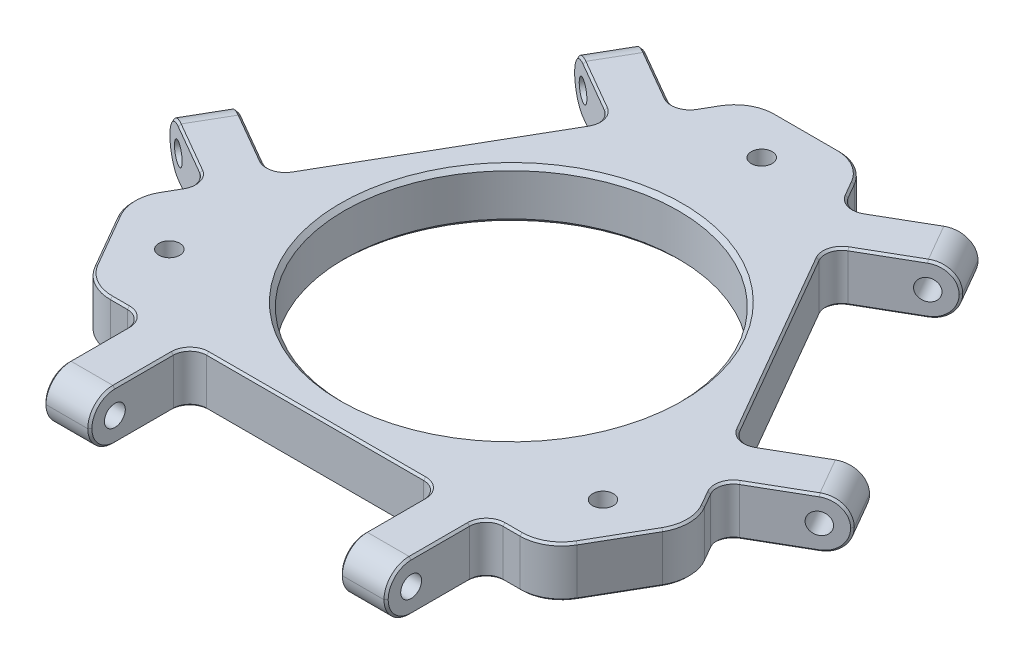
SolidWorks part; units mm, degrees
material "6061-T6 (SS)"
ref_plane "Front Plane" through (0, 0, 0) normal (0, 0, 1) x (1, 0, 0)
ref_plane "Top Plane" through (0, 0, 0) normal (0, 1, 0) x (1, 0, 0)
ref_plane "Right Plane" through (0, 0, 0) normal (1, 0, 0) x (0, 0, -1)
sketch "Sketch1" plane through (0, 0, 0) normal (0, 1, 0) x (1, 0, 0)
  line L1 (-20.5, 35.507) -> (-41, 0)
  line L2 (-41, 0) -> (-20.5, -35.507)
  line L3 (-20.5, -35.507) -> (20.5, -35.507)
  line L4 (20.5, -35.507) -> (41, 0)
  line L5 (41, 0) -> (20.5, 35.507)
  line L6 (20.5, 35.507) -> (-20.5, 35.507)
  circle A1 centre (0, 0) radius 35.507 construction
  dimension "D1" = 41
  dimension "D2" = 71.0141
extrude "Boss-Extrude1" add sketch "Sketch1" along normal blind 6
sketch "Sketch2" plane through (0, 6, 0) normal (0, 1, 0) x (1, 0, 0)
  line L0 (-20.5, -35.507) -> (-20.5, -23.507)
  line L1 (-20.5, -23.507) -> (-27.4282, -23.507)
  line L2 (20.5, -35.507) -> (20.5, -23.507)
  line L3 (20.5, -23.507) -> (27.4282, -23.507)
  line L4 (-20.5, -23.507) -> (-15, -23.507) construction
  line L5 (-15, -35.507) -> (15, -35.507)
  line L6 (20.5, 35.507) -> (-20.5, 35.507)
  line L7 (-20.5, 35.507) -> (-41, 0)
  line L8 (-41, 0) -> (-20.5, -35.507)
  line L9 (-20.5, -35.507) -> (20.5, -35.507)
  line L10 (20.5, -35.507) -> (41, 0)
  line L11 (41, 0) -> (20.5, 35.507)
  line L12 (20.5, 35.507) -> (-20.5, 35.507) construction
  line L13 (-20.5, 35.507) -> (-41, 0) construction
  line L14 (-41, 0) -> (-20.5, -35.507) construction
  line L15 (-20.5, -35.507) -> (20.5, -35.507) construction
  line L16 (20.5, -35.507) -> (41, 0) construction
  line L17 (41, 0) -> (20.5, 35.507) construction
  line L18 (-15, -35.507) -> (-15, -23.507)
  line L19 (-15, -23.507) -> (15, -23.507)
  line L20 (15, -35.507) -> (15, -23.507)
  line L21 (15, -23.507) -> (20.5, -23.507) construction
  line L22 (-27.4282, -23.507) -> (-20.5, -35.507)
  line L23 (27.4282, -23.507) -> (20.5, -35.507)
  line L24 (0, 0) -> (0, -35.507) construction
  line L25 (-20.5, 35.507) -> (-10.1077, 29.507)
  line L26 (-10.1077, 29.507) -> (-6.6436, 35.507)
  line L27 (-41, 0) -> (-30.6077, -6)
  line L28 (-30.6077, -6) -> (-34.0718, -12)
  line L29 (-23.25, 30.7439) -> (-38.25, 4.7631)
  line L30 (-23.25, 30.7439) -> (-12.8577, 24.7439)
  line L31 (-12.8577, 24.7439) -> (-27.8577, -1.2369)
  line L32 (-38.25, 4.7631) -> (-27.8577, -1.2369)
  line L33 (-6.6436, 35.507) -> (-20.5, 35.507)
  line L34 (-34.0718, -12) -> (-41, 0)
  line L35 (41, 0) -> (30.6077, -6)
  line L36 (30.6077, -6) -> (34.0718, -12)
  line L37 (20.5, 35.507) -> (10.1077, 29.507)
  line L38 (10.1077, 29.507) -> (6.6436, 35.507)
  line L39 (38.25, 4.7631) -> (23.25, 30.7439)
  line L40 (38.25, 4.7631) -> (27.8577, -1.2369)
  line L41 (27.8577, -1.2369) -> (12.8577, 24.7439)
  line L42 (23.25, 30.7439) -> (12.8577, 24.7439)
  line L43 (34.0718, -12) -> (41, 0)
  line L44 (6.6436, 35.507) -> (20.5, 35.507)
  point P14 (0, -23.507)
  point P41 (0, 0)
  dimension "D2" = 30
  dimension "D3" = 12
  dimension "D1" = 0
  dimension "D4" = 3
extrude "Cut-Extrude1" cut sketch "Sketch2" against normal through all
sketch "Sketch3" plane through (-20.5, 0, 0) normal (-1, 0, 0) x (0, 0, 1)
  line L0 (35.507, 3) -> (23.507, 3) construction
  line L1 (35.507, 6) -> (35.507, 0) construction
  line L2 (23.507, 0) -> (23.507, 6) construction
  line L3 (32.507, 6) -> (32.507, 0) construction
  line L4 (35.507, 6) -> (23.507, 6) construction
  line L5 (35.507, 0) -> (23.507, 0) construction
  point P12 (32.507, 3)
  dimension "D1" = 3
hole_wizard "M3x0.5 Tapped Hole1" positions "Sketch7" profile "Sketch6" tap size "M3x0.5" standard "ANSI Metric" end condition up to next
sketch "Sketch7" plane through (-20.5, 0, 0) normal (-1, 0, 0) x (0, 0, 1)
  point P0 (32.507, 3)
sketch "Sketch6" plane through (-20.5, 3, 32.507) normal (0, 1, 0) x (0, 0, 1)
  line L0 (0, 0) -> (0, 10.6975)
  line L1 (0, 10.6975) -> (1.25, 10.6975)
  line L2 (1.25, 10.6975) -> (1.25, 0)
  line L5 (1.25, 0) -> (0, 0)
  line L11 (0, -6.35) -> (0, 107.95) construction
  dimension "Thru Tap Drill Dia." = 2.5
  dimension "Thru Tap Drill Depth" = 10.6975
cosmetic thread "Hole Thread1" parameters "D2"=3
mirror "Mirror1" about plane through (0, 0, 0) normal (1, 0, 0) of "M3x0.5 Tapped Hole1"
ref_axis "Axis1" through (0, 0, 0) along (0, 1, 0)
pattern_circular "CirPattern1" count 3 over 360 about axis through (0, 0, 0) along (0, 1, 0) of "M3x0.5 Tapped Hole1", "Mirror1"
fillet "Fillet1" radius 3 12 edges at (-39.625, 0, -2.3816) (-21.875, 0, -33.1255) (17.75, 0, 35.507) (-17.75, 0, 35.507) (21.875, 0, -33.1255) (39.625, 0, -2.3816) (-39.625, 6, -2.3816) (17.75, 6, 35.507) (-17.75, 6, 35.507) (21.875, 6, -33.1255) (39.625, 6, -2.3816) (-21.875, 6, -33.1255)
sketch "Sketch9" plane through (0, 0, 0) normal (0, 1, 0) x (1, 0, 0)
  line L0 (0, 0) -> (-25.9808, -15) construction
  line L1 (0, 0) -> (0, 30) construction
  line L2 (0, 0) -> (25.9808, -15) construction
  circle A1 centre (0, 0) radius 30 construction
  dimension "D1" = 60
  dimension "D2" = 120
  dimension "D3" = 120
hole_wizard "M3x0.5 Tapped Hole2" positions "Sketch13" profile "Sketch12" tap size "M3x0.5" standard "ANSI Metric" end condition up to next
sketch "Sketch13" plane through (0, 0, 0) normal (0, -1, 0) x (-1, 0, 0)
  point P0 (25.9808, -15)
  point P3 (-25.9808, -15)
  point P6 (0, 30)
sketch "Sketch12" plane through (-25.9808, 0, 15) normal (1, 0, 0) x (0, 0, -1)
  line L0 (0, 0) -> (0, 6)
  line L1 (0, 6) -> (1.25, 6)
  line L2 (1.25, 6) -> (1.25, 0)
  line L5 (1.25, 0) -> (0, 0)
  line L11 (0, -6.35) -> (0, 107.95) construction
  dimension "Thru Tap Drill Dia." = 2.5
  dimension "Thru Tap Drill Depth" = 6
cosmetic thread "Hole Thread2" parameters "D2"=3
cosmetic thread "Hole Thread3" parameters "D2"=3
cosmetic thread "Hole Thread4" parameters "D2"=3
sketch "Sketch14" plane through (0, 6, 0) normal (0, 1, 0) x (1, 0, 0)
  circle A0 centre (0, 0) radius 20
  dimension "D1" = 40
extrude "Cut-Extrude2" cut sketch "Sketch14" against normal through all
fillet "Fillet2" radius 2 12 edges at (10.1077, 3, -29.507) (30.6077, 3, 6) (12.8577, 3, -24.7439) (27.8577, 3, 1.2369) (-10.1077, 3, -29.507) (-27.8577, 3, 1.2369) (-12.8577, 3, -24.7439) (20.5, 3, 23.507) (-30.6077, 3, 6) (15, 3, 23.507) (-15, 3, 23.507) (-20.5, 3, 23.507)
fillet "Fillet3" radius 5 6 edges at (34.0718, 3, 12) (27.4282, 3, 23.507) (6.6436, 3, -35.507) (-6.6436, 3, -35.507) (-34.0718, 3, 12) (-27.4282, 3, 23.507)
chamfer "Chamfer1" distance 0.5 angle 45 2 edges at (0, 0, 20) (0, 6, 20)
chamfer "Chamfer2" distance 0.25 angle 45 108 edges at (0, 0, 23.507) (14.4142, 0, 24.0928) (-14.4142, 0, 24.0928) (15, 0, 29.007) (-15, 0, 29.007) (15, 0.8787, 34.6284) (-15, 0.8787, 34.6284) (15, 5.1213, 34.6284) (-15, 5.1213, 34.6284) (15, 6, 29.007) (14.4142, 6, 24.0928) (0, 6, 23.507) (-14.4142, 6, 24.0928) (-15, 6, 29.007) (-27.0415, 0, 22.8372) (-33.2983, 0, 12) (-23.5207, 0, 23.507) (-32.1181, 0, 8.616) (-21.0858, 0, 24.0928) (-31.4079, 0, 6.2144) (-20.5, 0, 29.007) (-35.3708, 0, 3.25) (-20.5, 0.8787, 34.6284) (-40.239, 0.8787, 0.4393) (-20.5, 5.1213, 34.6284) (-40.239, 5.1213, 0.4393) (-20.5, 6, 29.007) (-21.0858, 6, 24.0928) (-23.5207, 6, 23.507) (-27.0415, 6, 22.8372) (-33.2983, 6, 12) (-32.1181, 6, 8.616) (-31.4079, 6, 6.2144) (-35.3708, 6, 3.25) (-20.3577, 0, -11.7535) (-28.0721, 0, 0.4367) (-13.6579, 0, -24.5295) (-32.6208, 0, -1.5131) (-17.6208, 0, -27.4939) (-37.489, 0.8787, -4.3238) (-22.489, 0.8787, -30.3046) (-37.489, 5.1213, -4.3238) (-22.489, 5.1213, -30.3046) (-32.6208, 6, -1.5131) (-28.0721, 6, 0.4367) (-20.3577, 6, -11.7535) (-13.6579, 6, -24.5295) (-17.6208, 6, -27.4939) (-6.2568, 0, -34.8372) (6.2568, 0, -34.8372) (-8.5973, 0, -32.1231) (8.5973, 0, -32.1231) (-10.3221, 0, -30.3072) (10.3221, 0, -30.3072) (-14.8708, 0, -32.257) (14.8708, 0, -32.257) (-19.739, 0.8787, -35.0677) (19.739, 0.8787, -35.0677) (-19.739, 5.1213, -35.0677) (19.739, 5.1213, -35.0677) (-14.8708, 6, -32.257) (-10.3221, 6, -30.3072) (-8.5973, 6, -32.1231) (-6.2568, 6, -34.8372) (6.2568, 6, -34.8372) (8.5973, 6, -32.1231) (10.3221, 6, -30.3072) (14.8708, 6, -32.257) (20.3577, 0, -11.7535) (13.6579, 0, -24.5295) (28.0721, 0, 0.4367) (17.6208, 0, -27.4939) (32.6208, 0, -1.5131) (22.489, 0.8787, -30.3046) (37.489, 0.8787, -4.3238) (22.489, 5.1213, -30.3046) (37.489, 5.1213, -4.3238) (17.6208, 6, -27.4939) (13.6579, 6, -24.5295) (20.3577, 6, -11.7535) (28.0721, 6, 0.4367) (32.6208, 6, -1.5131) (27.0415, 0, 22.8372) (33.2983, 0, 12) (23.5207, 0, 23.507) (32.1181, 0, 8.616) (21.0858, 0, 24.0928) (31.4079, 0, 6.2144) (20.5, 0, 29.007) (35.3708, 0, 3.25) (20.5, 0.8787, 34.6284) (40.239, 0.8787, 0.4393) (20.5, 5.1213, 34.6284) (40.239, 5.1213, 0.4393) (20.5, 6, 29.007) (21.0858, 6, 24.0928) (23.5207, 6, 23.507) (35.3708, 6, 3.25) (31.4079, 6, 6.2144) (32.1181, 6, 8.616) (33.2983, 6, 12) (27.0415, 6, 22.8372) (-30.75, 0, 17.7535) (-30.75, 6, 17.7535) (0, 0, -35.507) (0, 6, -35.507) (30.75, 0, 17.7535) (30.75, 6, 17.7535)
